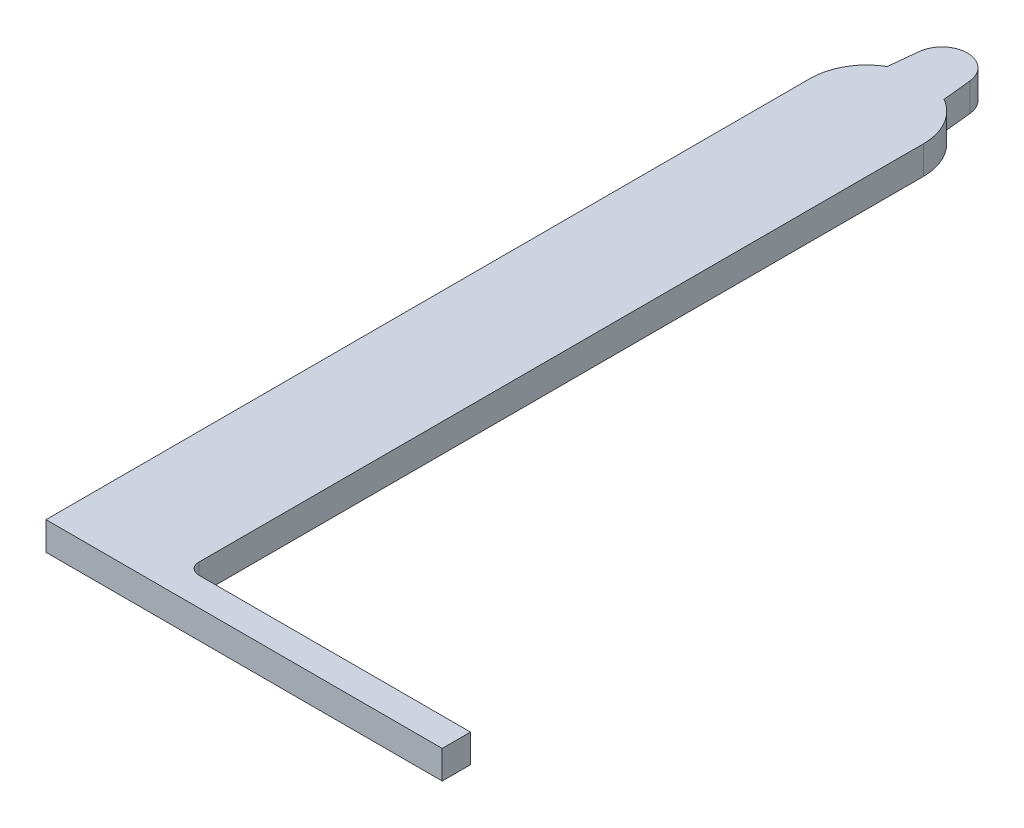
SolidWorks part; units mm, degrees
ref_plane "Front Plane" through (0, 0, 0) normal (0, 0, 1) x (1, 0, 0)
ref_plane "Top Plane" through (0, 0, 0) normal (0, 1, 0) x (1, 0, 0)
ref_plane "Right Plane" through (0, 0, 0) normal (1, 0, 0) x (0, 0, -1)
sketch "Sketch1" plane through (0, 0, 0) normal (0, 1, 0) x (1, 0, 0)
  line L1 (-12.7, 0) -> (12.7, 0)
  line L2 (-12.7, 0) -> (-12.7, -165.1)
  line L3 (-12.7, -165.1) -> (12.7, -165.1)
  line L4 (12.7, 0) -> (12.7, -165.1)
  circle A0 centre (0, 0) radius 12.7
  dimension "D1" = 25.4
  dimension "D2" = 165.1
extrude "Boss-Extrude1" add sketch "Sketch1" along normal blind 6.35 contours A0 L2 L3 L4 | L1 A0 | L1 A0 region at (0, 0, -5.39) region at (0, 0, 87.5114) region at (0, 0, 5.39)
sketch "Sketch2" plane through (0, 6.35, 0) normal (0, 1, 0) x (1, 0, 0)
  line L1 (-12.7, -165.1) -> (76.2, -165.1)
  line L2 (-12.7, -165.1) -> (-12.7, -171.45)
  line L3 (-12.7, -171.45) -> (76.2, -171.45)
  line L4 (76.2, -165.1) -> (76.2, -171.45)
  dimension "D1" = 88.9
  dimension "D2" = 6.35
extrude "Boss-Extrude2" add sketch "Sketch2" against normal up to surface (6.35 mm away) up to face at (0, 0, 79.375)
fillet "Fillet1" radius 2.54 1 edges
sketch "Sketch3" plane through (0, 0, 0) normal (0, -1, 0) x (-1, 0, 0)
  line L4 (-7.3841, 1.2138) -> (7.3841, 1.2138)
  line L6 (-7.3841, 1.2138) -> (-5.6981, 17.4684)
  line L7 (5.6981, 17.4684) -> (7.3841, 1.2138)
  line L8 (-7.3841, 1.2138) -> (-5.6981, 17.4684)
  line L9 (5.6981, 17.4684) -> (7.3841, 1.2138)
  arc A3 (5.6981, 17.4684) -> (-5.6981, 17.4684) centre (0, 16.8774) ccw
  arc A4 (5.6981, 17.4684) -> (-5.6981, 17.4684) centre (0, 16.8774) ccw
  dimension "D1" = 3.175
extrude "Boss-Extrude3" add sketch "Sketch3" against normal up to surface (6.35 mm away) up to face at (28.2277, 6.35, 106.0294)
